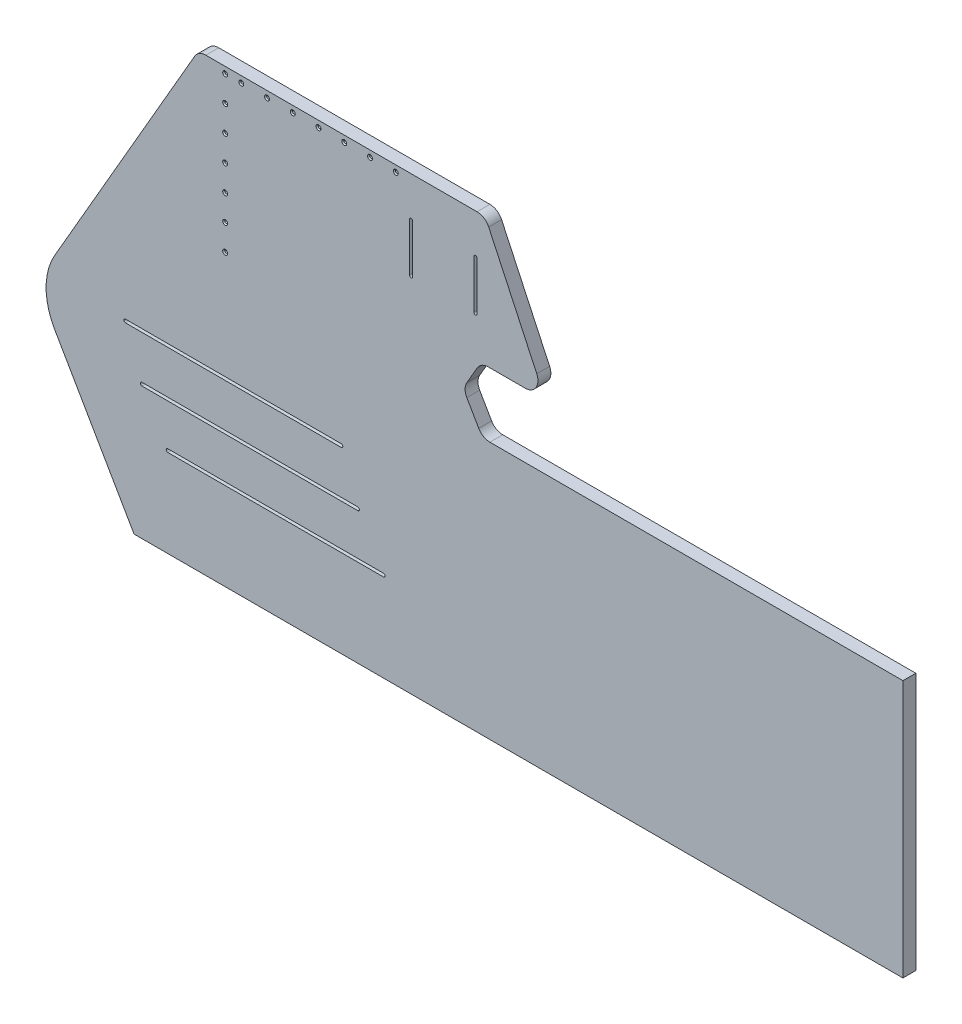
SolidWorks part; units mm, degrees
ref_plane "Front Plane" through (0, 0, 0) normal (0, 0, 1) x (1, 0, 0)
ref_plane "Top Plane" through (0, 0, 0) normal (0, 1, 0) x (1, 0, 0)
ref_plane "Right Plane" through (0, 0, 0) normal (1, 0, 0) x (0, 0, -1)
sketch "Sketch1" plane through (0, 0, 0) normal (0, 0, 1) x (1, 0, 0)
  line L12 (0, 0) -> (-193.1322, 334.5148)
  line L13 (-193.1322, 334.5148) -> (-19.647, 635)
  line L15 (107.353, 635) -> (-11.0891, 889)
  line L16 (-11.0891, 889) -> (-576.9054, 889)
  line L19 (-703.9054, 0) -> (0, 0)
  line L20 (-703.9054, 0) -> (-897.0376, 334.5148)
  line L21 (-897.0376, 334.5148) -> (-576.9054, 889)
  line L22 (-527.9291, -304.8) -> (-897.0376, 334.5148) construction
  line L23 (-193.1322, 334.5148) -> (-48.9764, 584.2) construction
  line L24 (-19.647, 635) -> (107.353, 635)
  line L25 (-897.0376, 334.5148) -> (-193.1322, 334.5148) construction
  dimension "D1" = 609.6
  dimension "D2" = 60
  dimension "D3" = 889
  dimension "D4" = 127
  dimension "D6" = 127
  dimension "D7" = 254
  dimension "D8" = 65
extrude "Boss-Extrude1" add sketch "Sketch1" along normal blind 25.4
fillet "Fillet1" radius 127 2 edges at (-193.1322, 334.5148, 12.7) (-897.0376, 334.5148, 12.7)
fillet "Fillet2" radius 25.4 4 edges at (107.353, 635, 12.7) (-576.9054, 889, 12.7) (-11.0891, 889, 12.7) (-19.647, 635, 12.7)
hole_wizard "wheel slot" positions "Sketch2" profile "Sketch3" size "1/4" standard "ANSI Inch" slot yes end condition through all
sketch "Sketch2" plane through (0, 0, 25.4) normal (0, 0, 1) x (1, 0, 0)
  line L0 (-30.3823, 711.2) -> (-30.3823, 812.8) construction
  line L1 (-4.9823, 635) -> (-4.9823, 889) construction
  line L2 (-4.9823, 889) -> (-27.2707, 889) construction
  line L4 (-30.3823, 762) -> (-4.9823, 762) construction
  line L6 (-157.3823, 762) -> (-30.3823, 762) construction
  point P0 (-30.3823, 762)
  point P4 (-157.3823, 762)
  dimension "D1" = 101.6
  dimension "D2" = 127
  dimension "D3" = 25.4
sketch "Sketch3" plane through (-30.3823, 762, 25.4) normal (1, 0, 0) x (0, -1, 0)
  line L0 (0, 0) -> (0, 25.4)
  line L1 (0, 25.4) -> (3.175, 25.4)
  line L2 (3.175, 25.4) -> (3.175, 0)
  line L5 (3.175, 0) -> (0, 0)
  line L11 (0, -6.35) -> (0, 107.95) construction
  dimension "Thru Hole Dia." = 6.35
  dimension "Thru Hole Depth" = 25.4
hole_wizard "pedal slot" positions "Sketch4" profile "Sketch5" size "1/4" standard "ANSI Inch" slot yes end condition through all
sketch "Sketch4" plane through (0, 0, 25.4) normal (0, 0, 1) x (1, 0, 0)
  line L0 (-640.4054, 175.9764) -> (-208.6054, 175.9764) construction
  line L6 (-475.3054, 263.9645) -> (-322.9054, 0)
  line L8 (-703.9054, 0) -> (0, 0) construction
  line L14 (-475.3054, 263.9645) -> (-508, 355.6)
  line L18 (-860.3759, 271.0148) -> (-703.9054, 0) construction
  point P0 (-424.5054, 175.9764)
  point P4 (-475.3054, 263.9645)
  point P47 (-508, 355.6)
  dimension "D1" = 431.8
  dimension "D3" = 203.2
  dimension "D4" = 101.6
  dimension "D5" = 355.6
  dimension "D2" = 381
  dimension "D6" = 508
sketch "Sketch5" plane through (-424.5054, 175.9764, 25.4) normal (1, 0, 0) x (0, -1, 0)
  line L0 (0, 0) -> (0, 25.4)
  line L1 (0, 25.4) -> (3.175, 25.4)
  line L2 (3.175, 25.4) -> (3.175, 0)
  line L5 (3.175, 0) -> (0, 0)
  line L11 (0, -6.35) -> (0, 107.95) construction
  dimension "Thru Hole Dia." = 6.35
  dimension "Thru Hole Depth" = 25.4
sketch "Sketch6" plane through (0, 0, 25.4) normal (0, 0, 1) x (1, 0, 0)
  line L0 (0, 0) -> (812.8, 0)
  line L1 (812.8, 0) -> (812.8, 508)
  line L2 (812.8, 508) -> (-16.6228, 508)
  line L3 (-16.6228, 508) -> (-54.7966, 574.119)
  line L4 (-156.4705, 398.0148) -> (-26.9793, 622.3) construction
  line L5 (0, 0) -> (-156.4705, 271.0148) construction
  line L6 (0, 0) -> (-156.4705, 271.0148)
  line L7 (-156.4705, 398.0148) -> (-54.7966, 574.119)
  arc A0 (-156.4705, 398.0148) -> (-156.4705, 271.0148) centre (-46.4852, 334.5148) ccw construction
  arc A1 (-156.4705, 398.0148) -> (-156.4705, 271.0148) centre (-46.4852, 334.5148) ccw
  dimension "D1" = 508
  dimension "D2" = 812.8
extrude "Boss-Extrude2" add sketch "Sketch6" against normal up to surface (25.4 mm away) up to face at (-424.5054, 175.9764, 0)
fillet "Fillet3" radius 25.4 2 edges at (-16.6228, 508, 12.7) (-54.7966, 574.119, 12.7)
hole_wizard "CSK for #10 Flat Head Machine Screw (100)1" positions "Sketch7" profile "Sketch8" countersink size "#10" standard "ANSI Inch" end condition through all
sketch "Sketch7" plane through (0, 0, 25.4) normal (0, 0, 1) x (1, 0, 0)
  line L0 (-524.1408, 889) -> (-524.1408, 876.3)
  line L4 (-524.1408, 876.3) -> (-524.1408, 825.5)
  line L5 (-524.1408, 876.3) -> (-492.3908, 876.3)
  line L6 (-492.3908, 876.3) -> (-441.5908, 876.3)
  line L7 (-441.5908, 876.3) -> (-390.7908, 876.3)
  line L8 (-390.7908, 876.3) -> (-339.9908, 876.3)
  line L9 (-339.9908, 876.3) -> (-289.1908, 876.3)
  line L10 (-289.1908, 876.3) -> (-238.3908, 876.3)
  line L11 (-524.1408, 825.5) -> (-524.1408, 774.7)
  line L12 (-524.1408, 774.7) -> (-524.1408, 723.9)
  line L13 (-524.1408, 723.9) -> (-524.1408, 673.1)
  line L14 (-524.1408, 673.1) -> (-524.1408, 622.3)
  line L15 (-524.1408, 622.3) -> (-524.1408, 571.5)
  line L16 (-238.3908, 876.3) -> (-187.5908, 876.3)
  line L17 (-27.2707, 889) -> (-562.2408, 889) construction
  arc A1 (-562.2408, 889) -> (-584.2378, 876.3) centre (-562.2408, 863.6) ccw construction
  point P0 (-524.1408, 876.3)
  point P13 (-524.1408, 825.5)
  point P17 (-492.3908, 876.3)
  point P19 (-441.5908, 876.3)
  point P20 (-390.7908, 876.3)
  point P21 (-339.9908, 876.3)
  point P22 (-289.1908, 876.3)
  point P24 (-238.3908, 876.3)
  point P41 (-524.1408, 774.7)
  point P43 (-524.1408, 723.9)
  point P45 (-524.1408, 673.1)
  point P47 (-524.1408, 622.3)
  point P49 (-524.1408, 571.5)
  point P74 (-187.5908, 876.3)
  point P75 (-548.9291, 889)
  dimension "D1" = 50.8
  dimension "D2" = 31.75
  dimension "D3" = 50.8
  dimension "D4" = 12.7
  dimension "D5" = 38.1
sketch "Sketch8" plane through (-524.1408, 876.3, 25.4) normal (1, 0, 0) x (0, -1, 0)
  line L0 (0, 0) -> (0, 25.4)
  line L1 (0, 25.4) -> (2.5527, 25.4)
  line L2 (2.5527, 25.4) -> (2.5527, 1.9608)
  line L3 (2.5527, 1.9608) -> (4.8895, 0)
  line L5 (4.8895, 0) -> (0, 0)
  line L6 (-2.5527, 1.9608) -> (-4.8895, 0) construction
  line L11 (0, -6.35) -> (0, 107.95) construction
  dimension "Thru Hole Dia." = 5.1054
  dimension "Thru Hole Depth" = 25.4
  dimension "Near C'Sink Dia." = 9.779
  dimension "Near C'Sink Angle" = 100
